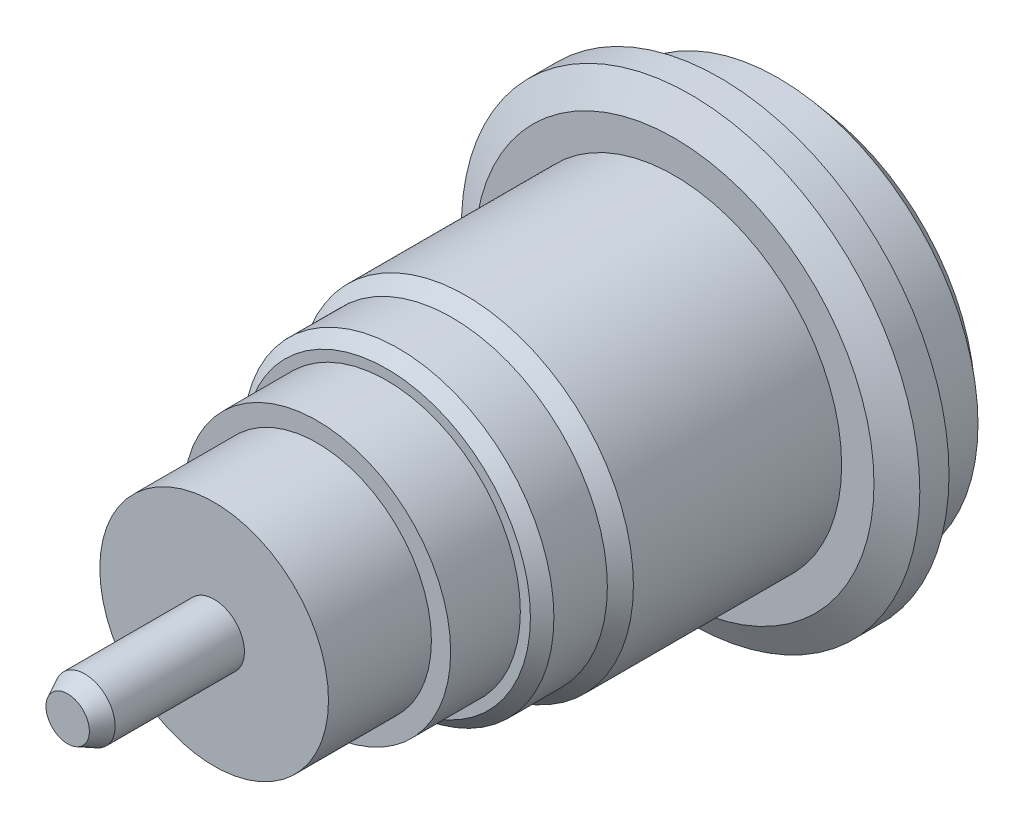
SolidWorks part; units mm, degrees
ref_plane "Front Plane" through (0, 0, 0) normal (0, 0, 1) x (1, 0, 0)
ref_plane "Top Plane" through (0, 0, 0) normal (0, 1, 0) x (1, 0, 0)
ref_plane "Right Plane" through (0, 0, 0) normal (1, 0, 0) x (0, 0, -1)
sketch "Sketch1" plane through (0, 0, 0) normal (1, 0, 0) x (0, 0, -1)
  line L0 (0, 9.5) -> (0, 7.4456)
  line L1 (224.503, 127.5793) -> (224.503, 46.6019) construction
  line L2 (0, 9.5) -> (1.1704, 9.5)
  line L3 (-42.4232, 0) -> (5.8689, 0) construction
  line L4 (-0.7715, 7.4456) -> (0, 7.4456)
  line L5 (-0.7715, 7.4456) -> (-0.7715, 6.8648)
  line L6 (-0.7715, 6.8648) -> (-4.0664, 6.8648)
  line L7 (-4.0664, 6.8648) -> (-4.0664, 8.4843)
  line L8 (-4.0664, 8.4843) -> (-4.9756, 9.5462)
  line L9 (-4.9756, 9.5462) -> (-7.0642, 9.5462)
  line L10 (-7.0642, 9.5462) -> (-7.7679, 10.9542)
  line L11 (-7.7679, 10.9542) -> (-9.164, 10.9542)
  line L12 (-9.164, 10.9542) -> (-9.9459, 9.5462)
  line L13 (-9.9459, 9.5462) -> (-9.9459, 8)
  line L14 (-9.9459, 8) -> (-19.8961, 8)
  line L15 (-19.8961, 8) -> (-20.5664, 7.426)
  line L16 (-20.5664, 7.426) -> (-23.1214, 7.426)
  line L17 (-23.1214, 7.426) -> (-23.6826, 6.8648)
  line L18 (-23.6826, 6.8648) -> (-23.6826, 6.3835)
  line L19 (-23.6826, 6.3835) -> (-27.0134, 6.3835)
  line L20 (-27.0134, 6.3835) -> (-27.0134, 5.4642)
  line L21 (-27.0134, 5.4642) -> (-31.932, 5.4642)
  line L22 (-31.932, 5.4642) -> (-31.932, 1.4475)
  line L23 (-31.932, 1.4475) -> (-38.1113, 1.4475)
  line L24 (-38.1113, 1.4475) -> (-38.932, 1.0374)
  line L25 (-38.932, 1.0374) -> (-38.932, 0)
  line L26 (-38.932, 0) -> (2.9336, 0)
  arc A0 (1.1704, 9.5) -> (2.9336, 0) centre (-23.54, 0) cw
  point P4 (0, 0)
  dimension "D1" = 7
  dimension "D2" = 16.5
  dimension "D3" = 19
  dimension "D4" = 16
  dimension "D5" = 7
revolve "Revolve2" add sketch "Sketch1" angle 360 about L26
split "Split1" bodies to split 101 resulting bodies 103 104 split by face at (8.4843, 0, 4.0664)
sketch "Sketch6" plane through (0, 0, 4.0664) normal (0, 0, -1) x (-1, 0, 0)
  circle A0 centre (0, 0) radius 6.8648
extrude "Cut-Extrude2" cut sketch "Sketch6" against normal blind 3.3
sketch "Sketch5" plane through (0, 0, 4.0664) normal (0, 0, -1) x (-1, 0, 0)
  circle A0 centre (0, 0) radius 50.4595
extrude "Cut-Extrude1" cut sketch "Sketch5" along normal blind 25
